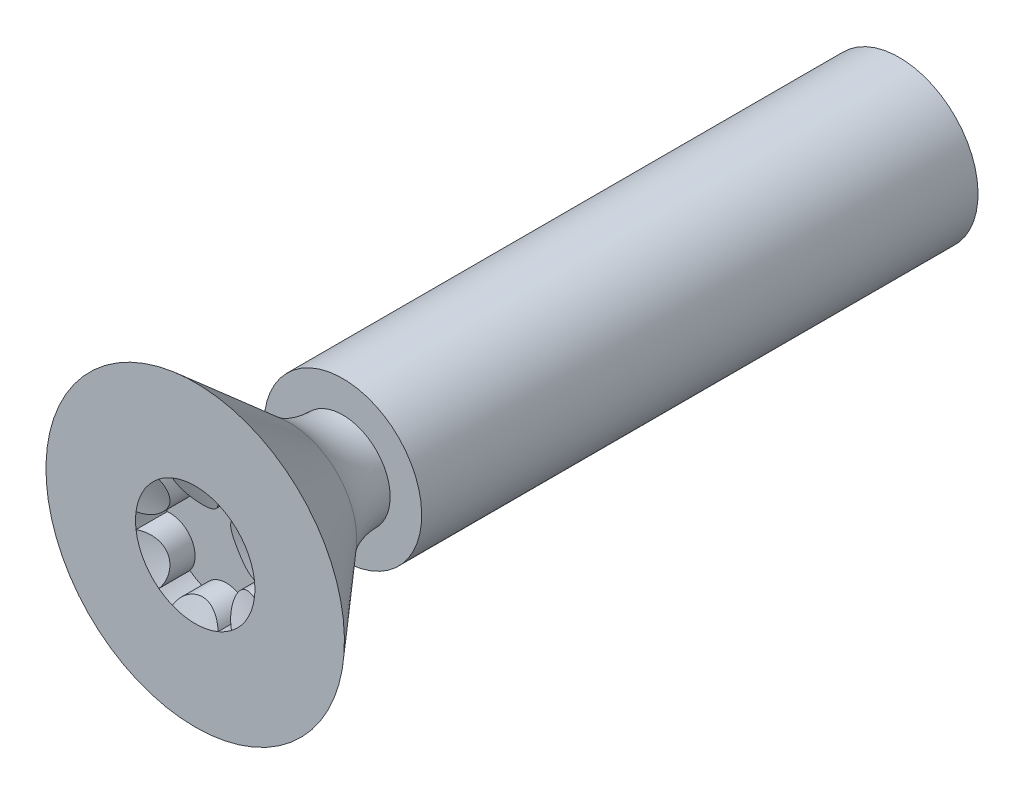
SolidWorks part; units mm, degrees
material "Plain Carbon Steel"
ref_plane "Front Plane" through (0, 0, 0) normal (0, 0, 1) x (1, 0, 0)
ref_plane "Top Plane" through (0, 0, 0) normal (0, 1, 0) x (1, 0, 0)
ref_plane "Right Plane" through (0, 0, 0) normal (1, 0, 0) x (0, 0, -1)
sketch "Sketch1" plane through (0, 0, 0) normal (1, 0, 0) x (0, 0, -1)
  line L0 (-6.35, 0) -> (6.35, 0) construction
  line L1 (6.35, 0) -> (6.35, 1.4224) construction
  line L2 (6.35, 1.4224) -> (-4.6482, 1.4224) construction
  line L4 (-6.35, 2.6924) -> (-6.35, 0) construction
  line L5 (6.35, -1.4224) -> (6.35, 1.4224) construction
  line L6 (6.2706, 1.5599) -> (6.9056, 0.46) construction
  line L7 (6.9056, 0.46) -> (7.5406, 1.5599) construction
  line L8 (7.5406, 1.5599) -> (6.2706, 1.5599) construction
  line L9 (6.9056, 0.46) -> (6.9056, 0.5975) construction
  line L10 (6.9056, 1.5599) -> (6.9056, 1.4224) construction
  line L11 (7.4612, 1.4224) -> (6.35, 1.4224) construction
  line L12 (6.9056, 1.4911) -> (7.5009, 1.4911) construction
  line L13 (6.9056, 1.4911) -> (6.3103, 1.4911) construction
  line L14 (6.8262, 0.5975) -> (6.985, 0.5975) construction
  line L15 (-6.35, 2.6924) -> (-4.6482, 0.7347) construction
  line L16 (4.445, 1.4224) -> (4.445, 0) construction
  line L17 (4.445, 1.4224) -> (5.08, 1.3104) construction
  line L18 (5.08, 1.3104) -> (5.715, 1.1985) construction
  line L19 (5.715, 1.1985) -> (6.35, 1.0865) construction
  line L20 (-6.35, 0.7347) -> (-4.6482, 0.7347) construction
  line L21 (-4.6482, 1.4224) -> (-4.6482, 0.7347) construction
  line L22 (-4.7514, 0.8534) -> (4.445, 0.8534) construction
  line L23 (-6.35, 2.6924) -> (-4.2345, 0.8534) construction
  line L24 (6.6785, 0.8534) -> (7.1328, 0.8534) construction
  line L25 (-4.0132, 1.4224) -> (-4.5822, 0.8534) construction
  line L26 (-6.35, 2.1336) -> (-3.9624, 0) construction
  line L27 (-6.35, 0.3683) -> (-4.3745, 0.3683) construction
  line L28 (-4.2345, 0.8534) -> (-3.2527, 0) construction
  line L30 (-3.6864, 0) -> (-3.6864, 1.4224) construction
  line L31 (-2.7339, 0) -> (-2.7339, 1.4224) construction
  arc A1 (-4.8191, 0.9313) -> (-4.6482, 0.8534) centre (-4.6482, 1.0799) ccw construction
  arc A2 (-4.6482, 1.213) -> (-3.6864, 0.8534) centre (-3.6864, 2.3195) ccw construction
  point P0 (2.54, 1.4224)
  point P4 (0, 0)
  point P10 (6.35, 0)
  point P41 (-4.4205, 1.0151)
  point P45 (-6.35, 1.077)
  point P55 (-5.8395, 0.7347)
  dimension "Length" = 12.7
  dimension "Screw OD" = 2.8448
  dimension "Head DIa" = 5.3848
  dimension "Pitch" = 1.27
  dimension "D2" = 0.1588
  dimension "D3" = 41
  dimension "D4" = 10
  dimension "D5" = 1.27
  dimension "Head Ht" = 1.7018
  dimension "D6" = 0.569
  dimension "D1" = 3.81
  dimension "D7" = 49
  dimension "D8" = 45
  dimension "D9" = 0.635
  dimension "D10" = 2.1539
  dimension "Recess Wd" = 0.7366
  dimension "Recess Dia" = 4.2672
  dimension "Recess Dp" = 2.3876
  dimension "D11" = 0.9525
  dimension "D12" = 0.5105
sketch "Sketch2" plane through (0, 0, 0) normal (0, 0, 1) x (1, 0, 0)
  line L0 (0, 0) -> (1.2318, -0.7112) construction
  line L1 (0, 0) -> (-1.2318, -0.7112) construction
  line L2 (0, 0.46) -> (0, 1.5599) construction
  line L5 (0, 2.6924) -> (0, 0) construction
  line L12 (0, 0) -> (0.5385, 0.9327) construction
  line L13 (0, 0) -> (-0.5385, 0.9327) construction
  line L14 (0, 0) -> (-0.4121, 0.995) construction
  line L15 (0, 0) -> (0.4121, 0.995) construction
  line L17 (0, -1.4224) -> (0, 1.4224) construction
  circle A7 centre (0, 0) radius 1.4224 construction
  circle A9 centre (0, 0) radius 1.077 construction
  arc A10 (-0.4121, 0.995) -> (0.4121, 0.995) centre (0, 1.1657) ccw construction
  arc A11 (-0.2886, 1.3437) -> (0.2886, 1.3437) centre (0, 0.8534) cw construction
  arc A12 (-1.308, -0.4219) -> (-1.0194, -0.9218) centre (-0.7391, -0.4267) ccw construction
  arc A13 (1.308, -0.4219) -> (1.0194, -0.9218) centre (0.7391, -0.4267) cw construction
  arc A14 (-1.308, -0.4219) -> (-0.2886, 1.3437) centre (0.7611, -0.4394) cw construction
  arc A15 (0.2886, 1.3437) -> (1.308, -0.4219) centre (-0.7611, -0.4394) cw construction
  arc A16 (1.0194, -0.9218) -> (-1.0194, -0.9218) centre (0, 0.8788) cw construction
  circle A17 centre (0, 0) radius 0.8534 construction
  point P0 (0, 2.6924)
  point P17 (1.2318, -0.7112)
  point P19 (-1.2318, -0.7112)
  point P21 (0, 0.8534)
  point P22 (1.2318, -0.7112)
  point P25 (0, -1.1904)
  point P26 (-1.2318, -0.7112)
  point P29 (0, 1.4224)
  point P66 (-0.7391, -0.4267)
  dimension "D1" = 0.569
  dimension "D2" = 120
  dimension "D3" = 120
  dimension "D6" = 7.5
  dimension "D7" = 7.5
  dimension "D8" = 30
  dimension "D9" = 30
  dimension "D4" = 0.0254
sketch "Sketch3" plane through (0, 0, 0) normal (1, 0, 0) x (0, 0, -1)
  line L0 (6.35, 0) -> (6.35, 1.4224) construction
  line L1 (-6.35, 0) -> (6.35, 0) construction
  line L2 (6.35, 1.4224) -> (-4.6482, 1.4224) construction
  line L3 (-3.6864, 1.4224) -> (-3.6864, 0.8534)
  line L4 (-6.35, 2.6924) -> (-6.35, 0) construction
  line L5 (6.35, 0) -> (6.35, 1.4224)
  line L6 (-6.35, 0) -> (6.35, 0)
  line L7 (6.35, 1.4224) -> (-3.6864, 1.4224)
  line L9 (-6.35, 2.6924) -> (-6.35, 0)
  line L15 (-6.35, 2.6924) -> (-4.2345, 0.8534) construction
  line L17 (-6.35, 2.6924) -> (-4.6482, 1.213)
  arc A0 (-4.6482, 1.213) -> (-3.6864, 0.8534) centre (-3.6864, 2.3195) ccw construction
  arc A1 (-4.6482, 1.213) -> (-3.6864, 0.8534) centre (-3.6864, 2.3195) ccw
revolve "Revolve1" add sketch "Sketch3" angle 360 about L0
ref_plane "Plane1" through (0, 0, 6.35) normal (0, 0, 1) x (1, 0, 0)
ref_plane "Plane5" through (0, 0, -4.445) normal (0, 0, 1) x (1, 0, 0)
ref_plane "Plane6" through (0, 0, 3.6864) normal (0, 0, 1) x (1, 0, 0)
ref_plane "Plane7" through (0, 0, 2.7339) normal (0, 0, 1) x (1, 0, 0)
sketch "Sketch21" plane through (0, 0, 6.35) normal (0, 0, 1) x (1, 0, 0)
  line L0 (0, 0) -> (-0.5385, 0.9327) construction
  line L3 (0, 0) -> (0.5385, 0.9327) construction
  line L4 (0, 0) -> (-0.5385, 0.9327)
  line L7 (0, 0) -> (0.5385, 0.9327)
  circle A0 centre (0, 0) radius 1.077 construction
  arc A1 (-0.4121, 0.995) -> (0.4121, 0.995) centre (0, 1.1657) ccw construction
  arc A2 (0.5385, 0.9327) -> (0.4121, 0.995) centre (0, 0) ccw
  arc A3 (-0.4121, 0.995) -> (0.4121, 0.995) centre (0, 1.1657) ccw
  arc A4 (-0.4121, 0.995) -> (-0.5385, 0.9327) centre (0, 0) ccw
extrude "Cut-Extrude14" cut sketch "Sketch21" against normal blind 0.5616
pattern_circular "CirPattern1" count 6 over 360 about axis through (0, 0, 6.35) along (0, 0, -1) of "Cut-Extrude14"
sketch "Sketch22" plane through (0, 0, 6.35) normal (0, 0, 1) x (1, 0, 0)
  circle A0 centre (0, 0) radius 1.077 construction
  circle A1 centre (0, 0) radius 1.077
extrude "Cut-Extrude15" cut sketch "Sketch22" against normal up to vertex (0.5105 mm away) draft 70 up to point (0, 0.7347, 5.8395)
sketch "Sketch20" plane through (0, 0, 0) normal (1, 0, 0) x (0, 0, -1)
  line L0 (6.35, -1.4224) -> (6.35, 1.4224) construction
  point P0 (4.445, -1.1904)
  dimension "D1" = 1.905
sketch "Sketch24" plane through (0, 0, 6.35) normal (0, 0, 1) x (1, 0, 0)
  circle A0 centre (0, 0) radius 2.6924
  point P0 (0.6556, -0.8544)
ref_axis "Center Axis 1" through (0, 0, 6.35) along (0, 0, -1)
ref_plane "Contact Plane 1" through (0, 0, -6.35) normal (0, 0, -1) x (-1, 0, 0)
ref_plane "Contact Plane 2" through (0, 0, 4.6482) normal (0, 0, 1) x (1, 0, 0)
sketch "Sketch8" [suppressed] plane through (0, 0, -6.35) normal (0, 0, -1) x (-1, 0, 0)
  line L0 (0, -1.4224) -> (0, 1.4224) construction
  circle A0 centre (0, 0) radius 1.4224
  point P0 (0, 1.4224)
curve "Helix/Spiral1" [suppressed] pitch 1.27 height 12.2682 turns 9.66
split "Split1" [suppressed] bodies to split 147
sketch "Sketch9" [suppressed] plane through (0, 0, 0) normal (1, 0, 0) x (0, 0, -1)
  line L0 (6.3103, 1.4911) -> (6.6785, 0.8534)
  line L2 (7.1328, 0.8534) -> (7.5009, 1.4911)
  line L3 (6.3103, 1.4911) -> (7.5009, 1.4911)
  line L5 (6.6785, 0.8534) -> (7.1328, 0.8534)
sweep "Cut-Sweep1" [suppressed] cut profiles "Sketch9" path "Helix/Spiral1"
sketch "Sketch11" [suppressed] plane through (0, 0, 3.6864) normal (0, 0, 1) x (1, 0, 0)
  arc A0 (1.0194, -0.9218) -> (1.308, -0.4219) centre (0.7391, -0.4267) ccw construction
  arc A1 (-1.0194, -0.9218) -> (1.0194, -0.9218) centre (0, 0.8788) ccw construction
  arc A2 (-1.308, -0.4219) -> (-1.0194, -0.9218) centre (-0.7391, -0.4267) ccw construction
  arc A3 (-0.2886, 1.3437) -> (-1.308, -0.4219) centre (0.7611, -0.4394) ccw construction
  arc A4 (0.2886, 1.3437) -> (-0.2886, 1.3437) centre (0, 0.8534) ccw construction
  arc A5 (1.308, -0.4219) -> (0.2886, 1.3437) centre (-0.7611, -0.4394) ccw construction
  arc A6 (1.0194, -0.9218) -> (1.308, -0.4219) centre (0.7391, -0.4267) ccw
  arc A7 (-1.0194, -0.9218) -> (1.0194, -0.9218) centre (0, 0.8788) ccw
  arc A8 (-1.308, -0.4219) -> (-1.0194, -0.9218) centre (-0.7391, -0.4267) ccw
  arc A9 (-0.2886, 1.3437) -> (-1.308, -0.4219) centre (0.7611, -0.4394) ccw
  arc A10 (0.2886, 1.3437) -> (-0.2886, 1.3437) centre (0, 0.8534) ccw
  arc A11 (1.308, -0.4219) -> (0.2886, 1.3437) centre (-0.7611, -0.4394) ccw
extrude "Cut-Extrude3" [suppressed] cut sketch "Sketch11" against normal through all flip side to cut
sketch "Sketch18" [suppressed] plane through (0, 0, 2.7339) normal (0, 0, 1) x (1, 0, 0)
  circle A0 centre (0, 0) radius 1.4224
  point P0 (0, 1.4224)
extrude "Cut-Extrude13" [suppressed] cut sketch "Sketch18" along normal through all draft 35.5 flip side to cut draft outward yes
sketch "Sketch12" [suppressed] plane through (0, 0, -4.445) normal (0, 0, 1) x (1, 0, 0)
  arc A0 (-1.308, -0.4219) -> (-1.0194, -0.9218) centre (-0.7391, -0.4267) ccw construction
  arc A1 (-1.0194, -0.9218) -> (1.0194, -0.9218) centre (0, 0.8788) ccw construction
  arc A2 (1.0194, -0.9218) -> (1.308, -0.4219) centre (0.7391, -0.4267) ccw construction
  arc A3 (1.308, -0.4219) -> (0.2886, 1.3437) centre (-0.7611, -0.4394) ccw construction
  arc A4 (0.2886, 1.3437) -> (-0.2886, 1.3437) centre (0, 0.8534) ccw construction
  arc A5 (-0.2886, 1.3437) -> (-1.308, -0.4219) centre (0.7611, -0.4394) ccw construction
  arc A6 (-1.308, -0.4219) -> (-1.0194, -0.9218) centre (-0.7391, -0.4267) ccw
  arc A7 (-1.0194, -0.9218) -> (1.0194, -0.9218) centre (0, 0.8788) ccw
  arc A8 (1.0194, -0.9218) -> (1.308, -0.4219) centre (0.7391, -0.4267) ccw
  arc A9 (1.308, -0.4219) -> (0.2886, 1.3437) centre (-0.7611, -0.4394) ccw
  arc A10 (0.2886, 1.3437) -> (-0.2886, 1.3437) centre (0, 0.8534) ccw
  arc A11 (-0.2886, 1.3437) -> (-1.308, -0.4219) centre (0.7611, -0.4394) ccw
extrude "Cut-Extrude4" [suppressed] cut sketch "Sketch12" against normal through all draft 7 flip side to cut draft outward yes
sketch "Sketch15" [suppressed] plane through (0, 0, 0) normal (1, 0, 0) x (0, 0, -1)
  line L14 (-2.8191, 0) -> (-3.6864, 0)
  line L17 (-3.6864, 0) -> (-3.6864, 0.8534)
  line L18 (-3.6864, 0.8534) -> (-2.8191, 0.8534)
  line L19 (-4.7514, 0.8534) -> (4.445, 0.8534) construction
  line L20 (-2.8191, 0.8534) -> (-2.8191, 0)
  point P3 (-3.2527, 0)
revolve "Revolve3" [suppressed] add sketch "Sketch15" angle 360 about L0
equation "\"D2@Sketch1\"=\"Pitch@Sketch1\"/8"
equation "\"D5@Sketch1\"=\"Pitch@Sketch1\""
equation "\"D6@Sketch1\"=\"Screw OD@Sketch1\"*.2"
equation "\"D9@Sketch1\"=\"Pitch@Sketch1\"*.5"
equation "\"D1@Sketch1\"=\"Pitch@Sketch1\"*3"
equation "\"D1@Sketch2\"=\"Screw OD@Sketch1\"*.2"
equation "\"D4@Helix/Spiral1\"=\"Pitch@Sketch1\""
equation "\"D3@Helix/Spiral1\"=\"Length@Sketch1\"-\"Head Ht@Sketch1\"+\"Pitch@Sketch1\""
equation "\"D10@Sketch1\"=\"Head DIa@Sketch1\"*.4"
equation "\"D11@Sketch1\"=\"Pitch@Sketch1\"*.75"
equation "\"D1@Sketch20\"=\"Pitch@Sketch1\"*1.5"
equation "\"D1@Cut-Extrude14\"=\"Head Ht@Sketch1\"*.33"
equation "\"D12@Sketch1\"=\"Head Ht@Sketch1\"*.3"
